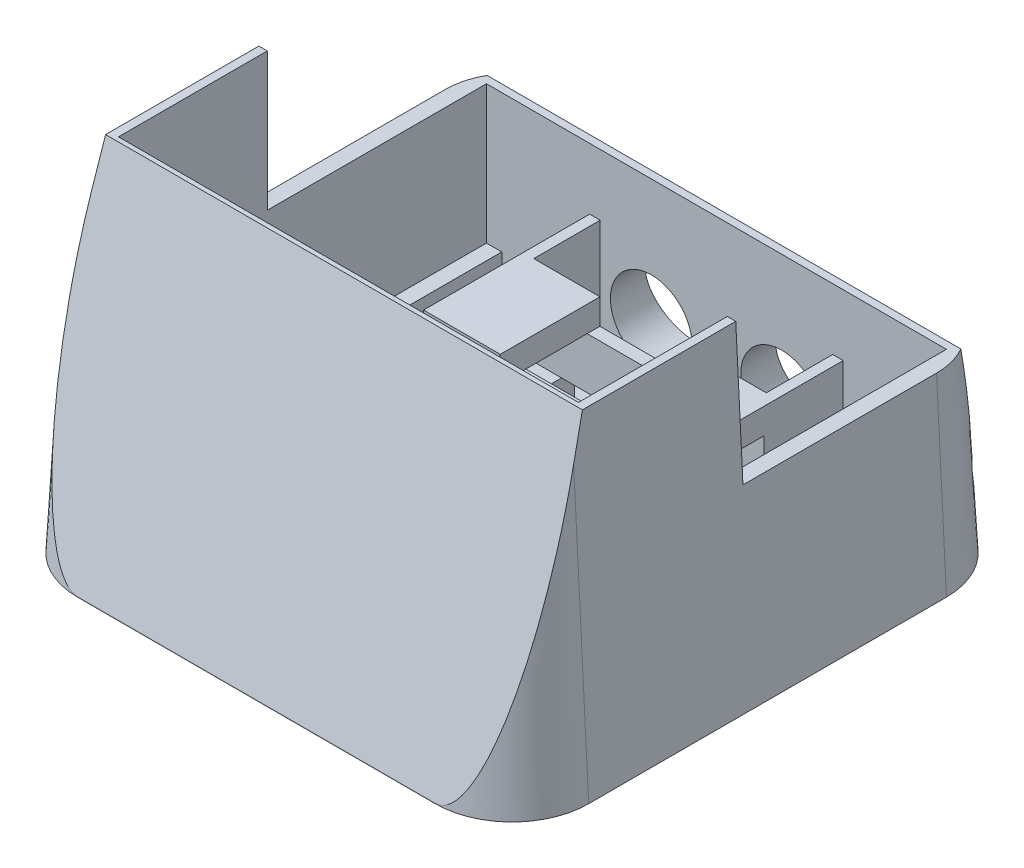
SolidWorks part; units mm, degrees
ref_plane "Front Plane" through (0, 0, 0) normal (0, 0, 1) x (1, 0, 0)
ref_plane "Top Plane" through (0, 0, 0) normal (0, 1, 0) x (1, 0, 0)
ref_plane "Right Plane" through (0, 0, 0) normal (1, 0, 0) x (0, 0, -1)
sketch "Sketch1" plane through (0, 0, 0) normal (0, 1, 0) x (1, 0, 0)
  line L0 (-35, 50) -> (35, 50)
  line L5 (50, 35) -> (50, -35)
  line L6 (-50, 35) -> (-50, -35)
  line L7 (-35, -50) -> (35, -50)
  arc A0 (35, -50) -> (50, -35) centre (35, -35) ccw
  arc A1 (-50, -35) -> (-35, -50) centre (-35, -35) ccw
  arc A2 (-50, 35) -> (-35, 50) centre (-35, 35) cw
  arc A3 (35, 50) -> (50, 35) centre (35, 35) cw
  point P14 (0, -50)
  point P19 (-50, 0)
  dimension "D3" = 15
  dimension "D4" = 15
  dimension "D5" = 15
  dimension "D6" = 15
  dimension "D1" = 100
  dimension "D2" = 100
extrude "Boss-Extrude1" add sketch "Sketch1" along normal blind 10
sketch "Sketch2" plane through (0, 10, 0) normal (0, 1, 0) x (1, 0, 0)
  line L0 (-50, 35) -> (-50, -35) construction
  line L1 (-42, 40) -> (-24.8, 40)
  line L2 (-42, 40) -> (-42, -3)
  line L3 (-42, -3) -> (-24.8, -3)
  line L4 (-24.8, 40) -> (-24.8, -3)
  line L5 (-42, 40) -> (-24.8, -3) construction
  line L6 (-42, -3) -> (-24.8, 40) construction
  line L7 (24.8, 40) -> (42, 40)
  line L8 (24.8, 40) -> (24.8, -3)
  line L9 (24.8, -3) -> (42, -3)
  line L10 (42, 40) -> (42, -3)
  line L11 (24.8, 40) -> (42, -3) construction
  line L12 (24.8, -3) -> (42, 40) construction
  line L13 (50, -35) -> (50, 35) construction
  line L15 (35, 50) -> (-35, 50) construction
  point P0 (-33.4, 18.5)
  point P5 (33.4, 18.5)
  dimension "D1" = 8
  dimension "D2" = 8
  dimension "D3" = 17.2
  dimension "D4" = 17.2
  dimension "D5" = 43
  dimension "D6" = 43
  dimension "D7" = 10
  dimension "D8" = 10
extrude "Cut-Extrude1" cut sketch "Sketch2" against normal through all
sketch "Sketch3" plane through (0, 10, 0) normal (0, 1, 0) x (1, 0, 0)
  line L1 (-40, -8) -> (40, -8)
  line L2 (-40, -8) -> (-40, -32)
  line L3 (-40, -32) -> (40, -32)
  line L4 (40, -8) -> (40, -32)
  line L5 (-40, -8) -> (40, -32) construction
  line L6 (-40, -32) -> (40, -8) construction
  line L7 (-45, -3) -> (45, -3)
  line L8 (-45, -3) -> (-45, -37)
  line L9 (-45, -37) -> (45, -37)
  line L10 (45, -3) -> (45, -37)
  line L11 (-45, -3) -> (45, -37) construction
  line L12 (-45, -37) -> (45, -3) construction
  line L13 (-35, -50) -> (35, -50) construction
  line L14 (-42, -3) -> (-24.8, -3) construction
  point P0 (0, -20)
  point P5 (0, -20)
  point P18 (0, -50)
  dimension "D1" = 24
  dimension "D2" = 80
  dimension "D3" = 34
  dimension "D4" = 90
extrude "Boss-Extrude3" add sketch "Sketch3" along normal blind 15
sketch "Sketch4" plane through (0, 10, 0) normal (0, 1, 0) x (1, 0, 0)
  line L0 (24.8, 40) -> (24.8, -3) construction
  line L3 (-24.8, 12.5) -> (24.8, 12.5)
  line L5 (-24.8, 24.5) -> (24.8, 24.5)
  line L6 (-24.8, 29.5) -> (24.8, 29.5)
  line L11 (-24.8, 7.5) -> (24.8, 7.5)
  line L12 (-24.8, 29.5) -> (-24.8, 24.5)
  line L13 (-24.8, -3) -> (-24.8, 40) construction
  line L14 (-24.8, 12.5) -> (-24.8, 7.5)
  line L15 (24.8, 12.5) -> (24.8, 7.5)
  line L16 (24.8, 29.5) -> (24.8, 24.5)
  point P4 (-24.8, 18.5)
  dimension "D1" = 5
  dimension "D2" = 12
  dimension "D3" = 5
  dimension "D4" = 6
extrude "Boss-Extrude4" add sketch "Sketch4" along normal blind 10
sketch "Sketch5" plane through (0, 20, 0) normal (0, 1, 0) x (1, 0, 0)
  line L0 (-24.8, 7.5) -> (24.8, 7.5) construction
  line L1 (-24.8, 29.5) -> (-9.8, 29.5)
  line L2 (-24.8, 29.5) -> (-24.8, 7.5)
  line L3 (-24.8, 7.5) -> (-9.8, 7.5)
  line L4 (-9.8, 29.5) -> (-9.8, 7.5)
  line L6 (24.8, 29.5) -> (9.8, 29.5)
  line L7 (24.8, 29.5) -> (24.8, 7.5)
  line L8 (24.8, 7.5) -> (9.8, 7.5)
  line L9 (9.8, 29.5) -> (9.8, 7.5)
  dimension "D1" = 15
  dimension "D2" = 15
extrude "Boss-Extrude5" add sketch "Sketch5" along normal blind 5
sketch "Sketch6" plane through (0, 10, 0) normal (0, 1, 0) x (1, 0, 0)
  line L1 (-45, -37) -> (45, -37)
  line L2 (-45, -37) -> (-45, 40)
  line L3 (-45, 40) -> (45, 40)
  line L4 (45, -37) -> (45, 40)
  line L5 (45, -37) -> (45, -3) construction
  line L6 (-24.8, 40) -> (-42, 40) construction
  line L7 (-50, 35) -> (-50, -35) construction
  line L8 (-35, -50) -> (35, -50) construction
  line L9 (50, -35) -> (50, 35) construction
  line L10 (35, 50) -> (-35, 50) construction
  line L11 (-50, 35) -> (-50, -35)
  line L12 (-35, -50) -> (35, -50)
  line L13 (50, -35) -> (50, 35)
  line L14 (35, 50) -> (-35, 50)
  arc A0 (-50, -35) -> (-35, -50) centre (-35, -35) ccw construction
  arc A1 (35, -50) -> (50, -35) centre (35, -35) ccw construction
  arc A2 (50, 35) -> (35, 50) centre (35, 35) ccw construction
  arc A3 (-35, 50) -> (-50, 35) centre (-35, 35) ccw construction
  arc A4 (-50, -35) -> (-35, -50) centre (-35, -35) ccw
  arc A5 (35, -50) -> (50, -35) centre (35, -35) ccw
  arc A6 (50, 35) -> (35, 50) centre (35, 35) ccw
  arc A7 (-35, 50) -> (-50, 35) centre (-35, 35) ccw
extrude "Boss-Extrude6" add sketch "Sketch6" along normal up to surface (15 mm away) up to face at (0, 25, 20)
sketch "Sketch9" plane through (0, 25, 0) normal (0, 1, 0) x (1, 0, 0)
  line L22 (-50, 35) -> (-50, -35) construction
  line L23 (-35, -50) -> (35, -50) construction
  line L24 (50, -35) -> (50, 35) construction
  line L25 (35, 50) -> (-35, 50) construction
  line L26 (-45, 35) -> (-45, -35)
  line L27 (-35, -45) -> (35, -45)
  line L28 (45, -35) -> (45, 35)
  line L29 (35, 45) -> (-35, 45)
  line L30 (-45, 35) -> (-45, -32)
  line L32 (45, -32) -> (45, 35)
  line L34 (-50, 35) -> (-50, -35)
  line L35 (-35, -50) -> (35, -50)
  line L36 (50, -35) -> (50, 35)
  line L37 (35, 50) -> (-35, 50)
  line L38 (45, -32) -> (-45, -32)
  line L39 (-40, -32) -> (40, -32) construction
  line L40 (43.6603, 40) -> (-43.6603, 40)
  line L41 (45, 40) -> (-45, 40) construction
  arc A23 (-50, -35) -> (-35, -50) centre (-35, -35) ccw construction
  arc A24 (35, -50) -> (50, -35) centre (35, -35) ccw construction
  arc A25 (50, 35) -> (35, 50) centre (35, 35) ccw construction
  arc A26 (-35, 50) -> (-50, 35) centre (-35, 35) ccw construction
  arc A27 (-45, -35) -> (-35, -45) centre (-35, -35) ccw
  arc A28 (35, -45) -> (45, -35) centre (35, -35) ccw
  arc A29 (45, 35) -> (35, 45) centre (35, 35) ccw
  arc A30 (-35, 45) -> (-45, 35) centre (-35, 35) ccw
  arc A33 (45, 35) -> (43.6603, 40) centre (35, 35) ccw
  arc A34 (-43.6603, 40) -> (-45, 35) centre (-35, 35) ccw
  arc A35 (-50, -35) -> (-35, -50) centre (-35, -35) ccw
  arc A36 (35, -50) -> (50, -35) centre (35, -35) ccw
  arc A37 (50, 35) -> (35, 50) centre (35, 35) ccw
  arc A38 (-35, 50) -> (-50, 35) centre (-35, 35) ccw
  dimension "D1" = 5
extrude "Boss-Extrude8" add sketch "Sketch9" along normal blind 39
chamfer "Chamfer1" distance 64 angle 3 8 edges at (0, 64, 50) (45.6066, 64, 45.6066) (-45.6066, 64, 45.6066) (50, 64, 0) (-50, 64, 0) (45.6066, 64, -45.6066) (-45.6066, 64, -45.6066) (0, 64, -50) first distance on face at (0, 32, 50) first distance on face at (44.0533, 32, 44.0533) first distance on face at (-44.0533, 32, 44.0533) first distance on face at (50, 32, 0) first distance on face at (-50, 32, 0) first distance on face at (44.0533, 32, -44.0533) first distance on face at (-44.0533, 32, -44.0533) first distance on face at (0, 32, -50)
chamfer "Chamfer2" distance 64 angle 10 1 edges at (0, 64, -46.6459) tangent propagation no first distance on face at (0, 32, -48.323)
chamfer "Chamfer3" distance 64 angle 12 1 edges at (0, 64, 46.6459) tangent propagation no first distance on face at (0, 32, 48.323)
sketch "Sketch10" plane through (0, 1.3075, 0) normal (-1, 0, 0) x (0, 0, 1)
  line L0 (-35, 62.6925) -> (32.8702, 62.6925) construction
  line L1 (2.8702, 62.6925) -> (-47.1298, 62.6925)
  line L2 (2.8702, 62.6925) -> (2.8702, 35.6925)
  line L3 (2.8702, 35.6925) -> (-47.1298, 35.6925)
  line L4 (-47.1298, 62.6925) -> (-47.1298, 35.6925)
  dimension "D1" = 50
  dimension "D2" = 27
  dimension "D3" = 30
extrude "Cut-Extrude3" cut sketch "Sketch10" against normal through all and the other way through all
sketch "Sketch11" plane through (0, 10, 0) normal (0, 1, 0) x (1, 0, 0)
  line L0 (24.8, 29.5) -> (-24.8, 29.5) construction
  line L1 (-22.75, 29.5) -> (22.75, 29.5)
  line L2 (-22.75, 29.5) -> (-22.75, 40)
  line L3 (-22.75, 40) -> (22.75, 40)
  line L4 (22.75, 29.5) -> (22.75, 40)
  line L5 (43.6603, 40) -> (-43.6603, 40) construction
  line L9 (24.8, 40) -> (-24.8, 40) construction
  point P10 (0, 40)
  point P11 (0, 29.5)
  dimension "D1" = 45.5
extrude "Cut-Extrude4" cut sketch "Sketch11" against normal blind 7.5
sketch "Sketch14" plane through (0, 10, 0) normal (0, 1, 0) x (1, 0, 0)
  line L0 (-24.8, 29.5) -> (-22.75, 29.5) construction
  line L1 (-22.75, 29.5) -> (-22.75, 40) construction
  line L2 (-22.75, 40) -> (-24.8, 40) construction
  line L3 (-24.8, 40) -> (-24.8, 29.5) construction
  line L4 (24.8, 40) -> (22.75, 40) construction
  line L5 (22.75, 40) -> (22.75, 29.5) construction
  line L6 (22.75, 29.5) -> (24.8, 29.5) construction
  line L7 (24.8, 29.5) -> (24.8, 40) construction
  line L8 (-24.8, 29.5) -> (-22.75, 29.5)
  line L9 (-22.75, 29.5) -> (-22.75, 40)
  line L10 (-22.75, 40) -> (-24.8, 40)
  line L11 (-24.8, 40) -> (-24.8, 29.5)
  line L12 (24.8, 40) -> (22.75, 40)
  line L13 (22.75, 40) -> (22.75, 29.5)
  line L14 (22.75, 29.5) -> (24.8, 29.5)
  line L15 (24.8, 29.5) -> (24.8, 40)
extrude "Boss-Extrude9" add sketch "Sketch14" along normal up to surface (15 mm away) up to face at (-17.3, 25, -18.5)
sketch "Sketch15" plane through (0, 0, -40) normal (0, 0, 1) x (1, 0, 0)
  line L0 (22.75, 2.5) -> (-22.75, 2.5) construction
  line L1 (12.75, 12.75) -> (-12.75, 12.75) construction
  line L2 (0, -35.2) -> (0, 35.2) construction
  circle A0 centre (-12.75, 12.75) radius 8
  circle A1 centre (12.75, 12.75) radius 8
  point P9 (0, 12.75)
  dimension "D3" = 16
  dimension "D4" = 16
  dimension "D1" = 10.25
  dimension "D2" = 10.25
  dimension "D5" = 25.5
extrude "Cut-Extrude5" cut sketch "Sketch15" against normal through all
sketch "Sketch17" plane through (0, 0, -29.5) normal (0, 0, -1) x (-1, 0, 0)
  line L8 (-9.8, 25) -> (-22.75, 25)
  line L9 (-22.75, 25) -> (-22.75, 2.5)
  line L10 (-22.75, 2.5) -> (22.75, 2.5)
  line L11 (22.75, 2.5) -> (22.75, 25)
  line L12 (22.75, 25) -> (9.8, 25)
  line L13 (9.8, 25) -> (9.8, 20)
  line L14 (9.8, 20) -> (-9.8, 20)
  line L15 (-9.8, 20) -> (-9.8, 25)
  line L16 (-9.8, 25) -> (-22.75, 25)
  line L17 (-22.75, 25) -> (-22.75, 2.5)
  line L18 (-22.75, 2.5) -> (22.75, 2.5)
  line L19 (22.75, 2.5) -> (22.75, 25)
  line L20 (22.75, 25) -> (9.8, 25)
  line L21 (9.8, 25) -> (9.8, 20)
  line L22 (9.8, 20) -> (-9.8, 20)
  line L23 (-9.8, 20) -> (-9.8, 25)
  dimension "D1" = 0
extrude "Cut-Extrude6" cut sketch "Sketch17" against normal blind 2.5
sketch "Sketch18" plane through (0, 0, 0) normal (0, -1, 0) x (1, 0, 0)
  line L1 (-14.8, -27) -> (14.8, -27)
  line L2 (-14.8, -27) -> (-14.8, 18)
  line L3 (-14.8, 18) -> (14.8, 18)
  line L4 (14.8, -27) -> (14.8, 18)
  line L5 (-24.8, 3) -> (-24.8, -40) construction
  line L6 (24.8, -40) -> (24.8, 3) construction
  line L8 (22.75, -27) -> (-22.75, -27) construction
  line L9 (24.8, 3) -> (42, 3) construction
  dimension "D1" = 10
  dimension "D2" = 10
  dimension "D3" = 15
extrude "Cut-Extrude7" cut sketch "Sketch18" against normal up to surface (10 mm away) up to face at (0, 10, -18.5)
sketch "Sketch20" plane through (0, 25, 0) normal (0, -1, 0) x (1, 0, 0)
  line L0 (-45, -35) -> (-45, -40) construction
  line L1 (-45, -40) -> (-43.6603, -40) construction
  line L2 (45, -40) -> (45, -35) construction
  line L3 (43.6603, -40) -> (45, -40) construction
  line L4 (-45, -35) -> (-45, -40)
  line L5 (-45, -40) -> (-43.6603, -40)
  line L6 (45, -40) -> (45, -35)
  line L7 (43.6603, -40) -> (45, -40)
  arc A0 (-45, -35) -> (-43.6603, -40) centre (-35, -35) ccw construction
  arc A1 (43.6603, -40) -> (45, -35) centre (35, -35) ccw construction
  arc A2 (-45, -35) -> (-43.6603, -40) centre (-35, -35) ccw
  arc A3 (43.6603, -40) -> (45, -35) centre (35, -35) ccw
extrude "Cut-Extrude8" cut sketch "Sketch20" against normal blind 15
sketch "Sketch21" plane through (0, 0, 0) normal (0, -1, 0) x (1, 0, 0)
  line L0 (-14.8, 18) -> (-14.8, -27) construction
  line L1 (-14.8, 18) -> (14.8, 18)
  line L2 (-14.8, 18) -> (-14.8, -17)
  line L3 (-14.8, -17) -> (14.8, -17)
  line L4 (14.8, 18) -> (14.8, -17)
  line L5 (14.8, -27) -> (14.8, 18) construction
  line L7 (-14.8, -27) -> (14.8, -27) construction
  line L8 (14.8, 18) -> (-14.8, 18) construction
  dimension "D2" = 10
extrude "Boss-Extrude10" add sketch "Sketch21" against normal blind 2.5
